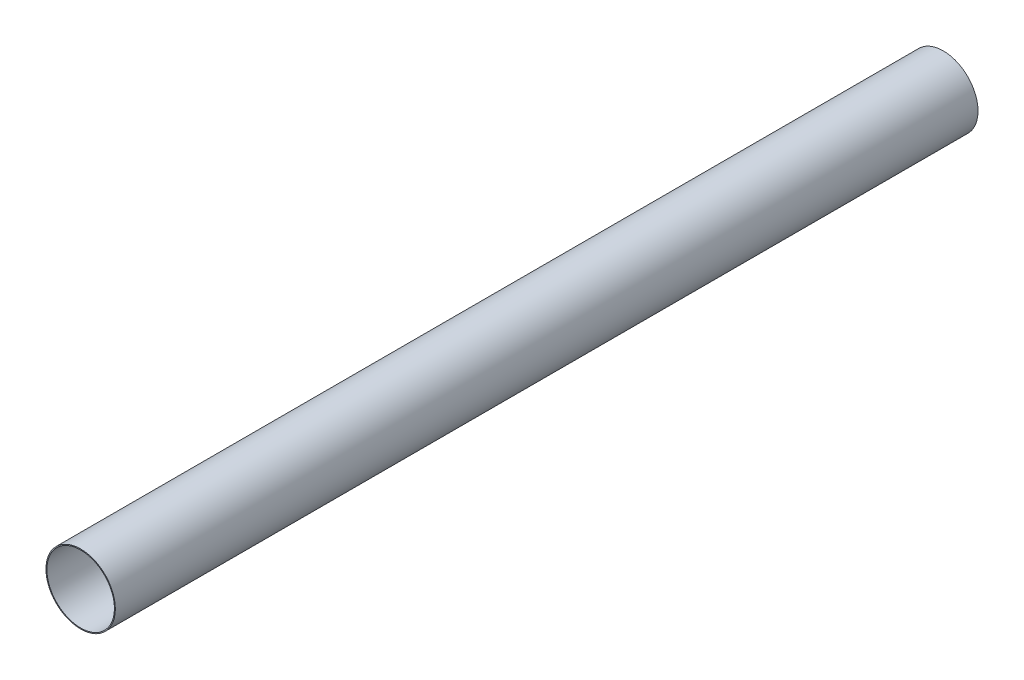
SolidWorks part; units mm, degrees
material "Fibra di Carbonio"
ref_plane "Front Plane" through (0, 0, 0) normal (0, 0, 1) x (1, 0, 0)
ref_plane "Top Plane" through (0, 0, 0) normal (0, 1, 0) x (1, 0, 0)
ref_plane "Right Plane" through (0, 0, 0) normal (1, 0, 0) x (0, 0, -1)
sketch "Sketch1" plane through (0, 0, 0) normal (0, 0, 1) x (1, 0, 0)
  circle A0 centre (0, 0) radius 73
  circle A1 centre (0, 0) radius 75
  dimension "D1" = 150
  dimension "D2" = 2
extrude "Boss-Extrude1" add sketch "Sketch1" along normal up to surface (1864 mm away)
